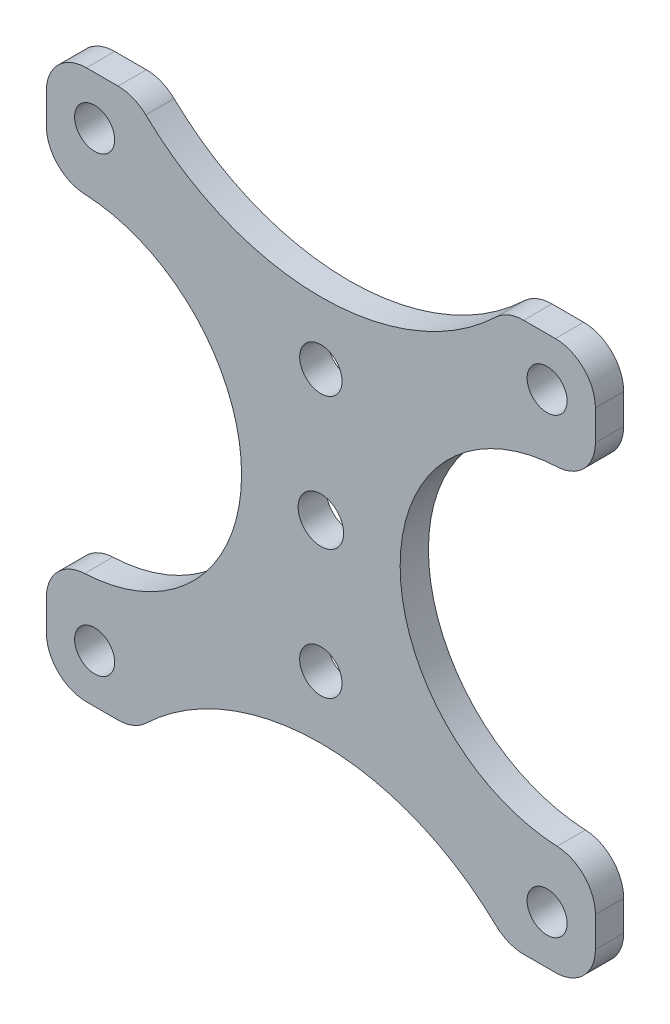
SolidWorks part; units mm, degrees
material "6061-T6 (SS)"
ref_plane "Front Plane" through (0, 0, 0) normal (0, 0, 1) x (1, 0, 0)
ref_plane "Top Plane" through (0, 0, 0) normal (0, 1, 0) x (1, 0, 0)
ref_plane "Right Plane" through (0, 0, 0) normal (1, 0, 0) x (0, 0, -1)
sketch "Sketch1" plane through (0, 0, 0) normal (0, 0, 1) x (1, 0, 0)
  line L0 (-30.8229, 30.8229) -> (30.8229, 30.8229)
  line L1 (30.8229, 30.8229) -> (30.8229, -30.8229)
  line L2 (30.8229, -30.8229) -> (-30.8229, -30.8229)
  line L3 (-30.8229, -30.8229) -> (-30.8229, 30.8229)
  line L4 (30.8229, -30.8229) -> (-30.8229, 30.8229) construction
  dimension "D2" = 61.6458
extrude "Boss-Extrude1" add sketch "Sketch1" along normal blind 3.175
hole_wizard "3/16 (0.1875) Diameter Hole1" positions "Sketch3" profile "Sketch2" hole size "3/16" standard "ANSI Inch" end condition through all
sketch "Sketch3" plane through (0, 0, 3.175) normal (0, 0, 1) x (1, 0, 0)
  line L2 (0, 14.685) -> (0, -14.685) construction
  point P0 (0, -14.685)
  point P2 (0, 14.685)
  dimension "D1" = 29.37
sketch "Sketch2" plane through (0, -14.685, 3.175) normal (1, 0, 0) x (0, -1, 0)
  line L0 (0, 0) -> (0, 3.175)
  line L1 (0, 3.175) -> (2.3812, 3.175)
  line L2 (2.3812, 3.175) -> (2.3812, 0)
  line L5 (2.3812, 0) -> (0, 0)
  line L11 (0, -6.35) -> (0, 107.95) construction
  dimension "Thru Hole Dia." = 4.7625
  dimension "Thru Hole Depth" = 3.175
hole_wizard "#8 Clearance Hole1" positions "Sketch6" profile "Sketch5" hole size "#8" standard "ANSI Inch" end condition through all
sketch "Sketch6" plane through (0, 0, 3.175) normal (0, 0, 1) x (1, 0, 0)
  line L0 (-25.4, 25.4) -> (25.4, 25.4) construction
  line L1 (25.4, 25.4) -> (25.4, -25.4) construction
  line L2 (25.4, -25.4) -> (-25.4, -25.4) construction
  line L3 (-25.4, -25.4) -> (-25.4, 25.4) construction
  line L6 (25.4, -25.4) -> (-25.4, 25.4) construction
  point P0 (-25.4, 25.4)
  point P2 (-25.4, -25.4)
  point P4 (25.4, -25.4)
  point P6 (25.4, 25.4)
  dimension "D1" = 50.8
sketch "Sketch5" plane through (-25.4, 25.4, 3.175) normal (1, 0, 0) x (0, -1, 0)
  line L0 (0, 0) -> (0, 3.175)
  line L1 (0, 3.175) -> (2.2479, 3.175)
  line L2 (2.2479, 3.175) -> (2.2479, 0)
  line L5 (2.2479, 0) -> (0, 0)
  line L11 (0, -6.35) -> (0, 107.95) construction
  dimension "Thru Hole Dia." = 4.4958
  dimension "Thru Hole Depth" = 3.175
hole_wizard "#10 Clearance Hole2" positions "Sketch8" profile "Sketch7" hole size "#10" standard "ANSI Inch" end condition through all
sketch "Sketch8" plane through (0, 0, 3.175) normal (0, 0, 1) x (1, 0, 0)
  line L0 (0, 14.685) -> (0, -14.685) construction
  point P0 (0, 0)
sketch "Sketch7" plane through (0, 0, 3.175) normal (1, 0, 0) x (0, -1, 0)
  line L0 (0, 0) -> (0, 3.175)
  line L1 (0, 3.175) -> (2.5527, 3.175)
  line L2 (2.5527, 3.175) -> (2.5527, 0)
  line L5 (2.5527, 0) -> (0, 0)
  line L11 (0, -6.35) -> (0, 107.95) construction
  dimension "Thru Hole Dia." = 5.1054
  dimension "Thru Hole Depth" = 3.175
fillet "Fillet1" radius 4.4958 4 edges at (-30.8229, -30.8229, 1.5875) (30.8229, -30.8229, 1.5875) (30.8229, 30.8229, 1.5875) (-30.8229, 30.8229, 1.5875)
sketch "Sketch9" plane through (0, 0, 3.175) normal (0, 0, 1) x (1, 0, 0)
  circle A0 centre (27.3685, 0) radius 18.4658
  circle A1 centre (0, 50.148) radius 28.4526
  circle A2 centre (25.4, 25.4) radius 7.0104 construction
  circle A3 centre (25.4, -25.4) radius 7.0104 construction
  circle A4 centre (0, 0) radius 8.9027 construction
  circle A5 centre (-25.4, 25.4) radius 7.0104 construction
  circle A6 centre (0, 14.685) radius 7.0104 construction
  circle A7 centre (25.4, 25.4) radius 2.2479 construction
  circle A8 centre (0, 0) radius 2.5527 construction
  dimension "D1" = 4.7625
  dimension "D2" = 6.35
ref_axis "Axis1" through (0, 0, -0.1588) along (0, 0, 1)
ref_plane "Plane1" through (0, 0, 0) normal (0.7071, 0.7071, 0) x (0, 0, 1)
extrude "Cut-Extrude2" cut sketch "Sketch9" against normal through all contours A1
extrude "Cut-Extrude3" cut sketch "Sketch9<4>" against normal through all contours A0
sketch "Sketch9<4>" plane through (0, 0, 3.175) normal (0, 0, 1) x (1, 0, 0) same geometry as "Sketch9"
mirror "Mirror1" about plane through (0, 0, 0) normal (0, 1, 0) of "Cut-Extrude2"
mirror "Mirror2" about plane through (0, 0, 0) normal (1, 0, 0) of "Cut-Extrude3"
fillet "Fillet3" radius 4.4958 8 edges at (-20.8828, 30.8229, 1.5875) (20.8828, 30.8229, 1.5875) (-30.8229, 18.1398, 1.5875) (-30.8229, -18.1398, 1.5875) (-20.8828, -30.8229, 1.5875) (20.8828, -30.8229, 1.5875) (30.8229, -18.1398, 1.5875) (30.8229, 18.1398, 1.5875)
